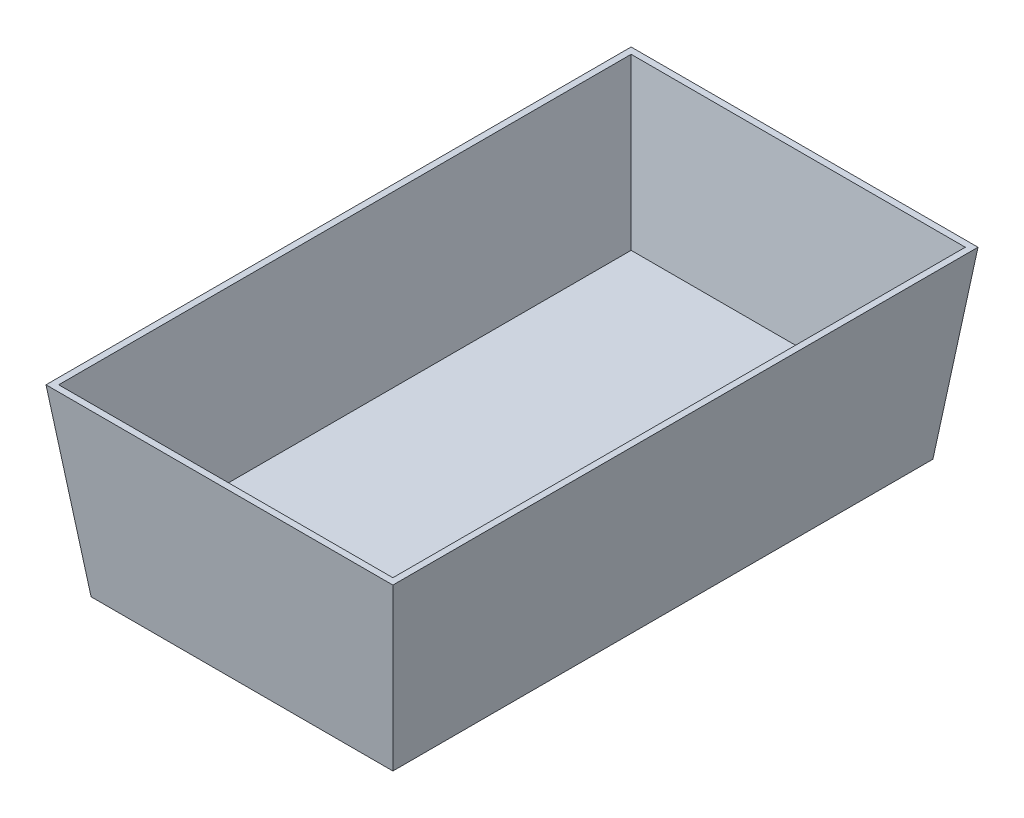
SolidWorks part; units mm, degrees
ref_plane "Спереди" through (0, 0, 0) normal (0, 0, 1) x (1, 0, 0)
ref_plane "Сверху" through (0, 0, 0) normal (0, 1, 0) x (1, 0, 0)
ref_plane "Справа" through (0, 0, 0) normal (1, 0, 0) x (0, 0, -1)
sketch "Эскиз1" plane through (0, 0, 0) normal (0, 1, 0) x (1, 0, 0)
  line L1 (-227.8958, 294.3477) -> (-702.8958, 294.3477)
  line L2 (-227.8958, 294.3477) -> (-227.8958, -555.6523)
  line L3 (-227.8958, -555.6523) -> (-702.8958, -555.6523)
  line L4 (-702.8958, 294.3477) -> (-702.8958, -555.6523)
  dimension "D1" = 850
  dimension "D2" = 475
extrude "Бобышка-Вытянуть1" add sketch "Эскиз1" along normal blind 289 draft 7 draft outward yes
sketch "Эскиз2" plane through (0, 289, 0) normal (0, 1, 0) x (1, 0, 0)
  line L0 (-192.411, 329.8324) -> (-738.3805, 329.8324) construction
  line L1 (-728.3805, 319.8324) -> (-202.411, 319.8324)
  line L2 (-728.3805, 319.8324) -> (-728.3805, -581.1371)
  line L3 (-728.3805, -581.1371) -> (-202.411, -581.1371)
  line L4 (-202.411, 319.8324) -> (-202.411, -581.1371)
  line L5 (-738.3805, 329.8324) -> (-738.3805, -591.1371) construction
  point P4 (-465.3958, 319.8324)
  point P7 (-465.3958, 329.8324)
  point P8 (-728.3805, -130.6523)
  point P11 (-738.3805, -130.6523)
  dimension "D1" = 10
  dimension "D2" = 10
extrude "Вырез-Вытянуть1" cut sketch "Эскиз2" against normal blind 238 draft 7
